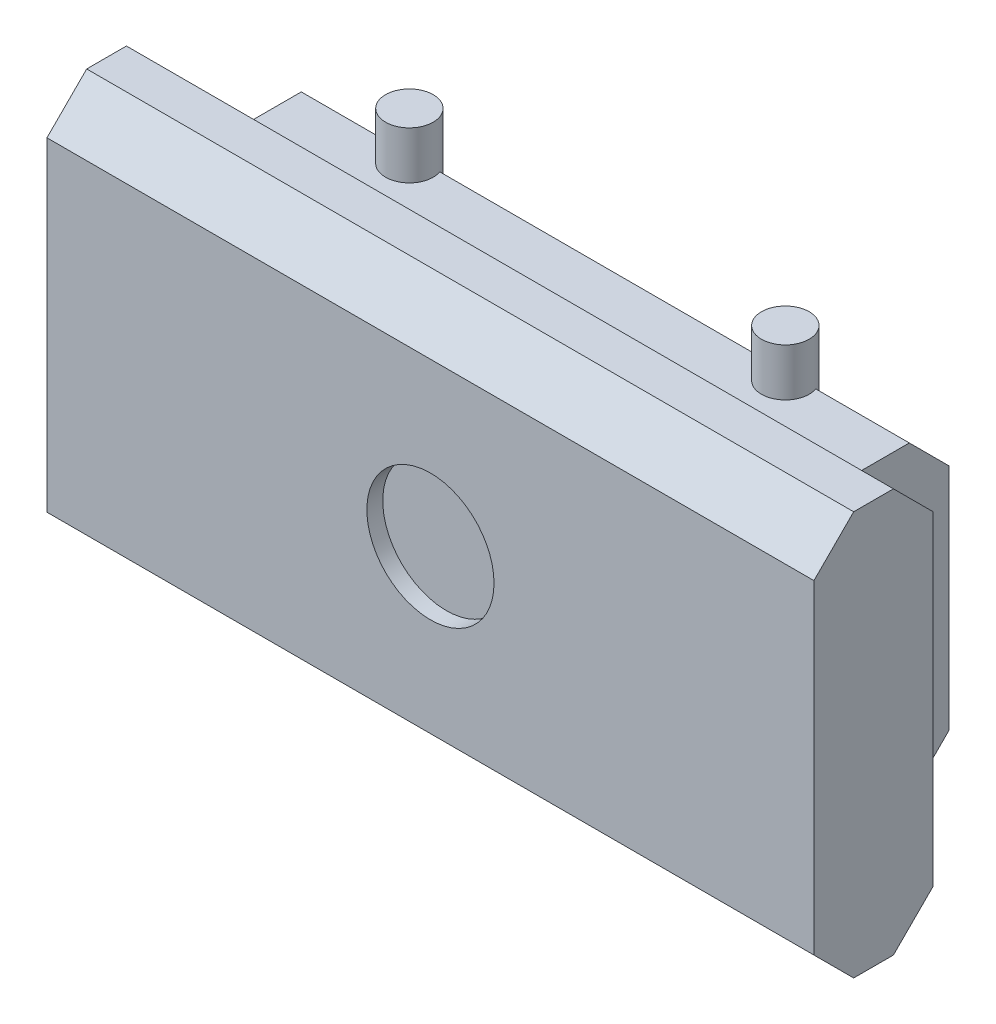
SolidWorks part; units mm, degrees
ref_plane "Front Plane" through (0, 0, 0) normal (0, 0, 1) x (1, 0, 0)
ref_plane "Top Plane" through (0, 0, 0) normal (0, 1, 0) x (1, 0, 0)
ref_plane "Right Plane" through (0, 0, 0) normal (1, 0, 0) x (0, 0, -1)
sketch "Sketch1" plane through (0, 0, 0) normal (0, 0, 1) x (1, 0, 0)
  line L1 (482.5, -254) -> (-482.5, -254)
  line L2 (482.5, -254) -> (482.5, 254)
  line L3 (482.5, 254) -> (-482.5, 254)
  line L4 (-482.5, -254) -> (-482.5, 254)
  line L5 (482.5, -254) -> (-482.5, 254) construction
  line L6 (482.5, 254) -> (-482.5, -254) construction
  point P0 (0, 0)
  dimension "D1" = 965
  dimension "D2" = 508
extrude "Boss-Extrude1" add sketch "Sketch1" along normal blind 150
sketch "Sketch2" plane through (0, 0, 0) normal (0, 0, 1) x (1, 0, 0)
  line L0 (482.5, 254) -> (-482.5, 254) construction
  line L1 (382.5, -194) -> (-382.5, -194)
  line L2 (382.5, -194) -> (382.5, 194)
  line L3 (382.5, 194) -> (-382.5, 194)
  line L4 (-382.5, -194) -> (-382.5, 194)
  line L5 (382.5, -194) -> (-382.5, 194) construction
  line L6 (382.5, 194) -> (-382.5, -194) construction
  line L7 (-482.5, 254) -> (-482.5, -254) construction
  point P0 (0, 0)
  dimension "D1" = 60
  dimension "D2" = 100
extrude "Boss-Extrude2" add sketch "Sketch2" against normal blind 120 separate body
sketch "Sketch3" plane through (0, -194, 0) normal (0, -1, 0) x (1, 0, 0)
  line L0 (382.5, -120) -> (382.5, 0) construction
  line L2 (-382.5, -120) -> (382.5, -120) construction
  circle A0 centre (236.5, -60) radius 30
  dimension "D3" = 60
  dimension "D1" = 146
  dimension "D2" = 60
extrude "Boss-Extrude3" add sketch "Sketch3" along normal blind 60 separate body
pattern_linear "LPattern2" count 2 spacing 448 along (0, 1, 0) count 2 spacing 473 along (-1, 0, 0) of "Boss-Extrude3"
combine bodies "Combine1" operation type add bodies to combine 101 102
combine bodies "Combine4" operation type add bodies to combine 110 103 107
combine bodies "Combine5" operation type add bodies to combine 108 109 111
chamfer "Chamfer1" distance 50 angle 45 6 edges at (0, -254, 150) (0, 254, 150) (0, -254, 0) (0, 254, 0) (0, -194, -120) (0, 194, -120)
sketch "Sketch4" plane through (-482.5, 0, 0) normal (-1, 0, 0) x (0, 0, 1)
  line L8 (0, 204) -> (0, -204)
  line L9 (0, -204) -> (50, -254)
  line L10 (50, -254) -> (100, -254)
  line L11 (100, -254) -> (150, -204)
  line L12 (150, -204) -> (150, 204)
  line L13 (150, 204) -> (100, 254)
  line L14 (100, 254) -> (50, 254)
  line L15 (50, 254) -> (0, 204)
  line L16 (0, 204) -> (0, -204)
  line L17 (0, -204) -> (50, -254)
  line L18 (50, -254) -> (100, -254)
  line L19 (100, -254) -> (150, -204)
  line L20 (150, -204) -> (150, 204)
  line L21 (150, 204) -> (100, 254)
  line L22 (100, 254) -> (50, 254)
  line L23 (50, 254) -> (0, 204)
  line L24 (50, -254) -> (100, -254)
  line L25 (0, -204) -> (50, -254)
  line L26 (0, 204) -> (0, -204)
  line L27 (50, 254) -> (0, 204)
  line L28 (100, 254) -> (50, 254)
  line L29 (150, 204) -> (100, 254)
  line L30 (150, -204) -> (150, 204)
  line L31 (100, -254) -> (150, -204)
  line L32 (50, -254) -> (100, -254)
  line L33 (0, -204) -> (50, -254)
  line L34 (0, 204) -> (0, -204)
  line L35 (50, 254) -> (0, 204)
  line L36 (100, 254) -> (50, 254)
  line L37 (150, 204) -> (100, 254)
  line L38 (150, -204) -> (150, 204)
  line L39 (100, -254) -> (150, -204)
  circle A0 centre (75, -114) radius 60
  circle A1 centre (75, 114) radius 60
  circle A2 centre (75, -114) radius 40
  circle A3 centre (75, 114) radius 40
  dimension "D5" = 120
  dimension "D6" = 120
  dimension "D9" = 20
  dimension "D10" = 20
  dimension "D2" = 0
  dimension "D3" = 75
  dimension "D4" = 75
  dimension "D7" = 140
  dimension "D8" = 140
  dimension "D1" = 0
extrude "Boss-Extrude4" add sketch "Sketch4" along normal blind 10 contours A1 A3 | A0 A2 region at (-482.5, -114, 16.6971) region at (-482.5, 114, 16.6971)
sketch "Sketch5" plane through (0, 0, 150) normal (0, 0, 1) x (1, 0, 0)
  circle A0 centre (0, 0) radius 80
  dimension "D1" = 160
extrude "Cut-Extrude1" cut sketch "Sketch5" against normal blind 20
